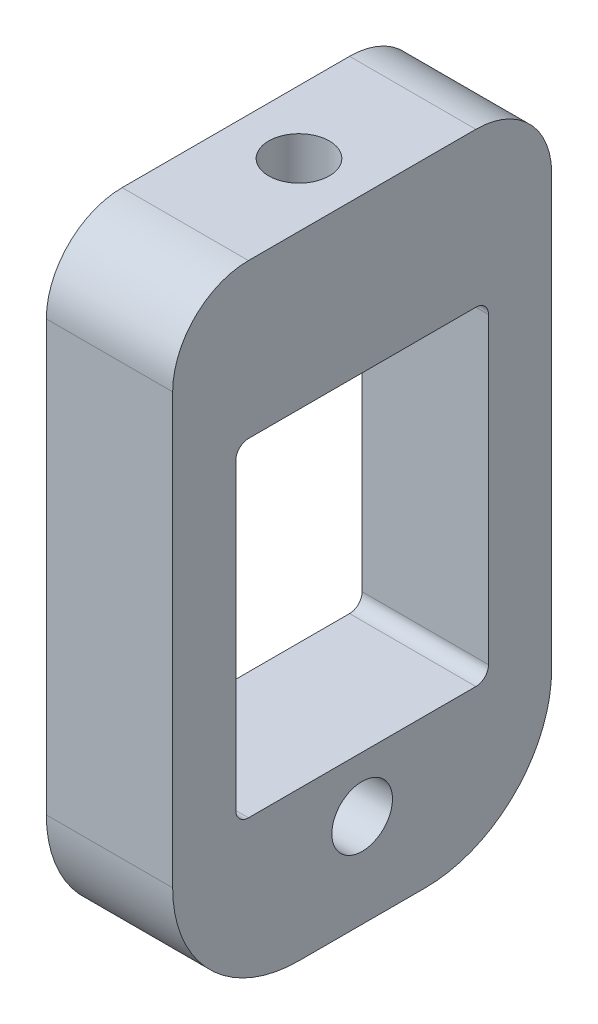
SolidWorks part; units mm, degrees
other "Markup1"
sketch "Sketch6" plane through (-4, 8, -3.5) normal (-0.1216, 0.9914, -0.0475) x (-0.0131, 0.0463, 0.9988)
material "7075 T651 protolabs"
ref_plane "Front Plane" through (0, 0, 0) normal (0, 0, 1) x (1, 0, 0)
ref_plane "Top Plane" through (0, 0, 0) normal (0, 1, 0) x (1, 0, 0)
ref_plane "Right Plane" through (0, 0, 0) normal (1, 0, 0) x (0, 0, -1)
sketch "Sketch16" plane through (0, 0, 0) normal (0, 1, 0) x (1, 0, 0)
  line L1 (-2.5, -7.5) -> (2.5, -7.5)
  line L2 (-2.5, -7.5) -> (-2.5, 7.5)
  line L3 (-2.5, 7.5) -> (2.5, 7.5)
  line L4 (2.5, -7.5) -> (2.5, 7.5)
  line L5 (-2.5, -7.5) -> (2.5, 7.5) construction
  line L6 (-2.5, 7.5) -> (2.5, -7.5) construction
  point P0 (0, 0)
  dimension "D1" = 15
  dimension "D2" = 5
extrude "Main Extrude_Locking" add sketch "Sketch16" along normal blind 25
sketch "Sketch18" plane through (-2.5, 0, 0) normal (-1, 0, 0) x (0, 0, 1)
  line L0 (0, 0) -> (0, 2.5) construction
  line L1 (-7.5, 0) -> (7.5, 0) construction
  circle A0 centre (0, 3.7) radius 1.2
  point P6 (0, 0)
  dimension "D2" = 2.4
  dimension "D1" = 2.5
extrude "Cut-Extrude1" cut sketch "Sketch18" against normal up to surface (5 mm away) up to face at (2.5, 12.5, 0)
sketch "Sketch8" plane through (-2.5, 0, 0) normal (-1, 0, 0) x (0, 0, 1)
  line L0 (0, 4.9) -> (-7.5, 4.9) construction
  line L1 (-7.5, 25) -> (-7.5, 0) construction
  line L3 (5, 5.9) -> (-5, 5.9)
  line L4 (5, 5.9) -> (5, 18.9)
  line L5 (5, 18.9) -> (-5, 18.9)
  line L6 (-5, 5.9) -> (-5, 18.9)
  line L7 (5, 5.9) -> (-5, 18.9) construction
  line L8 (5, 18.9) -> (-5, 5.9) construction
  circle A0 centre (0, 3.7) radius 1.2 construction
  point P6 (0, 12.4)
  point P12 (0, 0)
  dimension "D1" = 2
  dimension "D2" = 13
  dimension "D3" = 10
extrude "Cut-Extrude2" cut sketch "Sketch8" against normal up to surface (5 mm away) up to face at (2.5, 3.7, 1.2)
sketch "Sketch9" plane through (0, 25, 0) normal (0, 1, 0) x (1, 0, 0)
  circle A0 centre (0, 0) radius 1.2
  dimension "D1" = 2.4
extrude "Cut-Extrude3" cut sketch "Sketch9" against normal up to surface (6.1 mm away) up to face at (0, 18.9, 0)
fillet "Fillet1" radius 5 2 edges at (0, 0, 7.5) (0, 0, -7.5)
fillet "Fillet2" radius 3 2 edges at (0, 25, -7.5) (0, 25, 7.5)
fillet "Fillet3" radius 0.5 4 edges at (0, 18.9, 5) (0, 18.9, -5) (0, 5.9, -5) (0, 5.9, 5)
